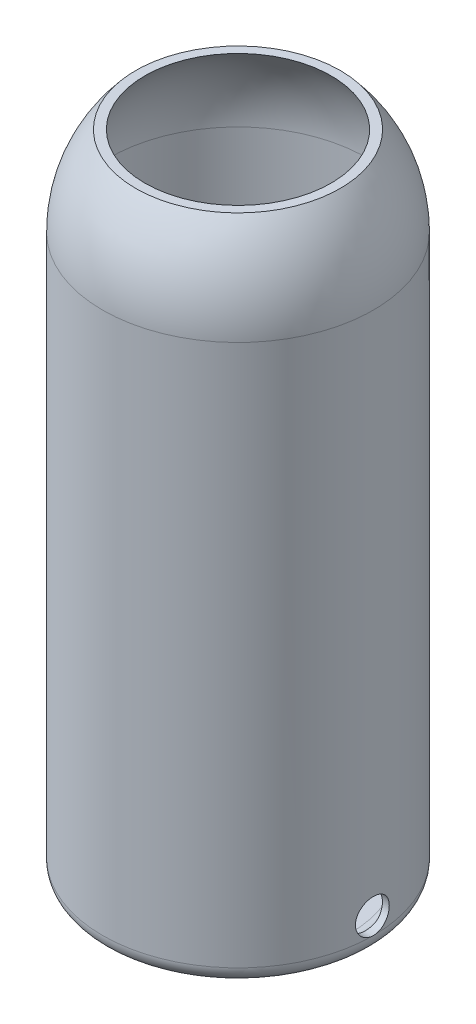
SolidWorks part; units mm, degrees
ref_plane "Front Plane" through (0, 0, 0) normal (0, 0, 1) x (1, 0, 0)
ref_plane "Top Plane" through (0, 0, 0) normal (0, 1, 0) x (1, 0, 0)
ref_plane "Right Plane" through (0, 0, 0) normal (1, 0, 0) x (0, 0, -1)
sketch "Sketch3" plane through (0, 0, 0) normal (1, 0, 0) x (0, 0, -1)
  line L1 (40, 0) -> (75, 0)
  line L4 (80, 5) -> (80, 165)
  line L6 (42, 2) -> (73, 2)
  line L7 (78, 7) -> (78, 165)
  line L9 (42, 2) -> (40, 2)
  line L10 (40, 2) -> (40, 0)
  line L11 (40, 205) -> (40, 0) construction
  line L12 (42, 202.9473) -> (42, 2) construction
  line L13 (40, 0) -> (80, 0) construction
  line L14 (80, 0) -> (80, 165) construction
  line L15 (42, 2) -> (78, 2) construction
  line L16 (78, 2) -> (78, 165) construction
  line L17 (40, 250.6943) -> (40, -21.3407) construction
  line L26 (70.2035, 191.225) -> (67.5, 191.225)
  arc A0 (80, 165) -> (70.2035, 191.225) centre (40, 165) ccw
  arc A2 (78, 165) -> (67.5, 191.225) centre (40, 165) ccw
  arc A3 (75, 0) -> (80, 5) centre (75, 5) ccw
  arc A4 (73, 2) -> (78, 7) centre (73, 7) ccw
  arc A6 (80, 165) -> (40, 205) centre (40, 165) ccw construction
  arc A7 (78, 165) -> (42, 202.9473) centre (40, 165) ccw construction
  dimension "D4" = 80
  dimension "D1" = 2
  dimension "D3" = 5
  dimension "D6" = 40
revolve "Revolve4" add sketch "Sketch3" angle 360 about L17
sketch "Sketch5" plane through (0, 0, 0) normal (1, 0, 0) x (0, 0, -1)
  circle A0 centre (40, 10) radius 5
  circle A1 centre (40, 10) radius 2.5
  dimension "D2" = 10
  dimension "D3" = 5
  dimension "D1" = 10
extrude "Cut-Extrude1" cut sketch "Sketch5" along normal blind 50 contours A1 | A0 A1 region at (0, 10, -35.1414) region at (0, 10, -40)
extrude "Cut-Extrude2" cut sketch "Sketch5<3>" against normal blind 50 contours A1 region at (0, 10, -40)
sketch "Sketch5<3>" plane through (0, 0, 0) normal (1, 0, 0) x (0, 0, -1) same geometry as "Sketch5"
